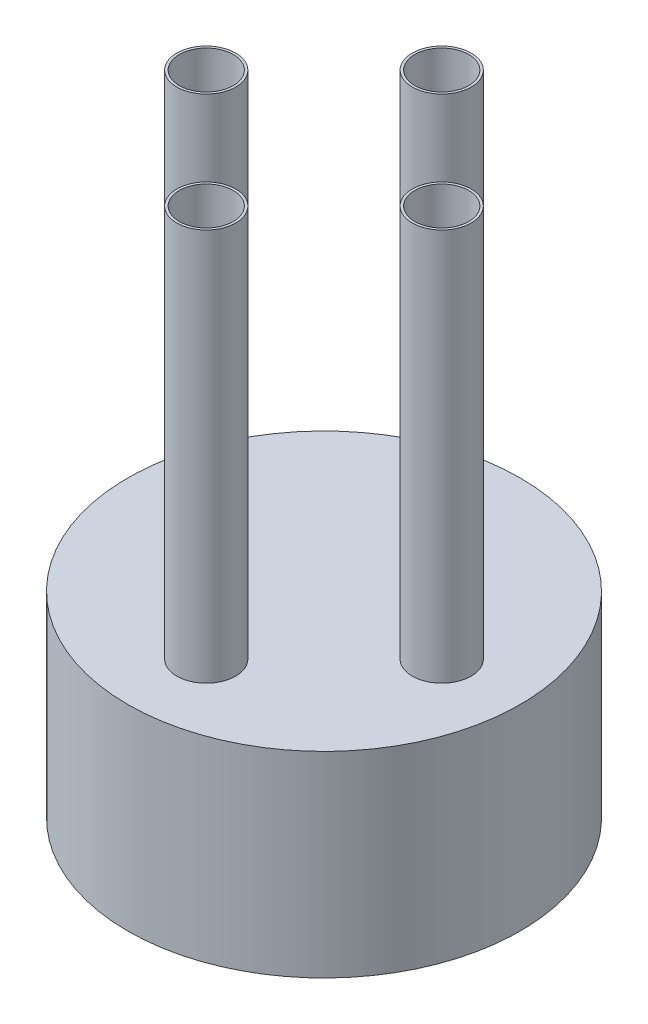
SolidWorks part; units mm, degrees
material "Glass"
ref_plane "Front Plane" through (0, 0, 0) normal (0, 0, 1) x (1, 0, 0)
ref_plane "Top Plane" through (0, 0, 0) normal (0, 1, 0) x (1, 0, 0)
ref_plane "Right Plane" through (0, 0, 0) normal (1, 0, 0) x (0, 0, -1)
sketch "Sketch1" plane through (0, 0, 0) normal (0, 1, 0) x (1, 0, 0)
  line L0 (0, 100) -> (0, -100) construction
  circle A0 centre (0, 0) radius 100
  dimension "D1" = 200
extrude "Boss-Extrude1" add sketch "Sketch1" along normal blind 100
sketch "Sketch3" plane through (0, 100, 0) normal (0, 1, 0) x (1, 0, 0)
  line L0 (0, 60) -> (0, -60) construction
  line L1 (-60, 0) -> (60, 0) construction
  circle A0 centre (0, 60) radius 15
  circle A1 centre (60, 0) radius 15
  circle A2 centre (0, -60) radius 15
  circle A3 centre (-60, 0) radius 15
  circle A4 centre (0, 60) radius 13.75
  circle A5 centre (60, 0) radius 13.75
  circle A6 centre (0, -60) radius 13.75
  circle A7 centre (-60, 0) radius 13.75
  point P4 (0, 0)
  point P8 (0, 0)
  point P17 (0, 0)
  point P24 (0, 0)
  dimension "D1" = 30
  dimension "D2" = 60
  dimension "D4" = 27.5
  dimension "D3" = 4
  dimension "D5" = 4
extrude "Boss-Extrude3" add sketch "Sketch3" along normal blind 200
sketch "Sketch5" plane through (0, 100, 0) normal (0, 1, 0) x (1, 0, 0)
  line L0 (0, -60) -> (0, 60) construction
  line L1 (-60, 0) -> (60, 0) construction
  circle A0 centre (0, 60) radius 13.75
  circle A1 centre (60, 0) radius 13.75
  circle A2 centre (0, -60) radius 13.75
  circle A3 centre (-60, 0) radius 13.75
  point P7 (0, 0)
  point P8 (0, 0)
  point P18 (0, 0)
  dimension "D1" = 27.5
  dimension "D2" = 4
extrude "Cut-Extrude1" cut sketch "Sketch5" against normal up to surface (100 mm away) up to face at (0, 0, 100)
sketch "Sketch6" plane through (0, 0, 0) normal (0, -1, 0) x (1, 0, 0)
  line L0 (0, 100) -> (0, -100) construction
  circle A0 centre (0, 0) radius 100 construction
  point P4 (0, 0)
